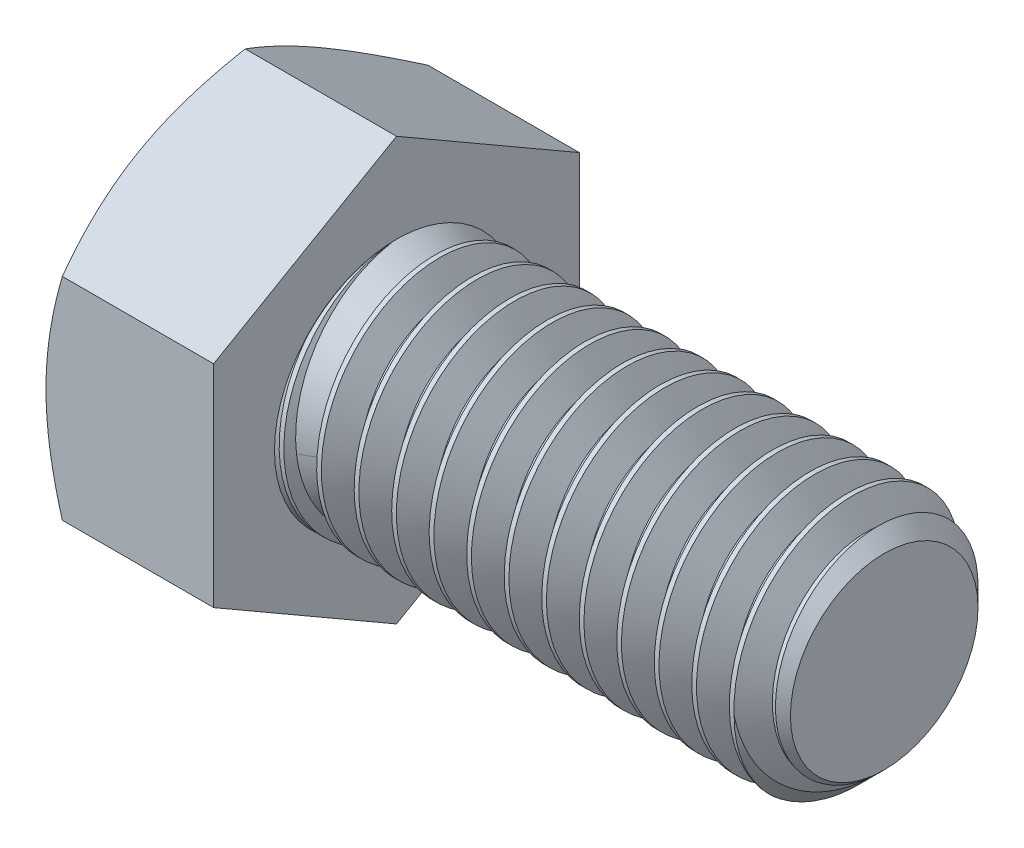
SolidWorks part; units mm, degrees
note: '?' marks a value the reader was unsure of.
ref_plane "Front Plane" through (0, 0, 0) normal (0, 0, 1) x (1, 0, 0)
ref_plane "Top Plane" through (0, 0, 0) normal (0, 1, 0) x (1, 0, 0)
ref_plane "Right Plane" through (0, 0, 0) normal (1, 0, 0) x (0, 0, -1)
sketch "Sketch1" plane through (0, 0, 0) normal (0, 0, 1) x (1, 0, 0)
  line L0 (-17.0656, 0) -> (17.0656, 0) construction
  line L1 (17.0656, 6.35) -> (17.0656, -6.35) construction
  line L2 (-8.3344, 9.525) -> (-8.3344, -9.525) construction
  line L3 (-17.0656, 9.525) -> (-17.0656, -9.525) construction
  line L4 (-8.5884, 6.3562) -> (-8.3344, 6.3562) construction
  line L5 (-8.3344, 6.3562) -> (2.6749, 0) construction
  line L6 (-8.5884, 6.3562) -> (-8.5884, 0) construction
  line L7 (-8.3344, 0) -> (-8.3344, 6.3562) construction
  point P9 (-8.3344, 0)
  point P10 (10.2272, -6.35)
  dimension "Screw Dia" = 12.7
  dimension "Hex" = 19.05
  dimension "Head Ht" = 8.7312
  dimension "Screw Length" = 25.4
  dimension "D1" = 6.8385
  dimension "D2" = 30
  dimension "D3" = 0.254
  dimension "MinThread" = 25.4
  dimension "D4" = 0.0124
ref_plane "Plane2" through (17.0656, 0, 0) normal (1, 0, 0) x (0, 0, -1)
sketch "Sketch5" plane through (17.0656, 0, 0) normal (1, 0, 0) x (0, 0, -1)
  circle A0 centre (0, 0) radius 6.35
extrude "Boss-Extrude3" add sketch "Sketch5" against normal up to vertex (25.4 mm away) up to point (-8.3344, 0, 0)
sketch "Sketch9" plane through (17.0656, 0, 0) normal (1, 0, 0) x (0, 0, -1)
  circle A1 centre (0, 0) radius 6.35
  circle A2 centre (0, 0) radius 6.35
  dimension "D1" = 0
chamfer "Chamfer1" distance 1.4654 angle 45 1 edges at (17.0656, 0, -6.35)
sketch "Sketch6" plane through (-8.3344, 0, 0) normal (-1, 0, 0) x (0, 0, 1)
  line L0 (0, 9.525) -> (0, -9.525) construction
  line L1 (9.525, 5.4993) -> (0, 10.9985)
  line L2 (0, 10.9985) -> (-9.525, 5.4993)
  line L3 (-9.525, 5.4993) -> (-9.525, -5.4993)
  line L4 (-9.525, -5.4993) -> (0, -10.9985)
  line L5 (0, -10.9985) -> (9.525, -5.4993)
  line L6 (9.525, -5.4993) -> (9.525, 5.4993)
  circle A0 centre (0, 0) radius 9.525 construction
extrude "Boss-Extrude4" add sketch "Sketch6" along normal up to vertex (8.7312 mm away) separate body up to point (-17.0656, -9.525, 0)
sketch "Sketch7" plane through (-17.0656, 0, 0) normal (-1, 0, 0) x (0, 0, 1)
  circle A0 centre (0, 0) radius 9.525 construction
  circle A1 centre (0, 0) radius 9.525
sketch "Sketch8" plane through (-17.0656, 0, 0) normal (-1, 0, 0) x (0, 0, 1)
  circle A0 centre (0, 0) radius 9.525 construction
  circle A1 centre (0, 0) radius 9.525
extrude "Cut-Extrude3" cut sketch "Sketch8" against normal through all draft 60 flip side to cut
sketch "Sketch12" plane through (-17.0656, 0, 0) normal (-1, 0, 0) x (0, 0, 1)
  line L0 (0, 7.3342) -> (0, 4.0958) construction
  line L1 (0.2857, 7.3342) -> (0.2858, 4.0958)
  line L2 (-0.2858, 7.3342) -> (-0.2857, 4.0958)
  line L3 (0, 6.35) -> (0, -6.35) construction
  arc A0 (0.2857, 7.3342) -> (-0.2858, 7.3342) centre (0, 7.3342) ccw
  arc A1 (-0.2857, 4.0958) -> (0.2858, 4.0958) centre (0, 4.0958) ccw
  circle A3 centre (0, 0) radius 3.81 construction
  circle A4 centre (0, 0) radius 7.62 construction
  point P2 (0, 5.715)
  dimension "D1" = 7.62
  dimension "D3" = 15.24
  dimension "D2" = 0.5715
extrude "Cut-Extrude4" cut sketch "Sketch12" against normal blind 0.254
pattern_circular "CirPattern1" count 6 over 360 about axis through (0, 0, 0) along (1, 0, 0) of "Cut-Extrude4"
curve "Helix/Spiral1" pitch 1.9538 height 27.3538 turns 14 parameters "Pitch"=1.9538
sketch "Sketch10" plane through (0, 0, 0) normal (0, 0, 1) x (1, 0, 0)
  line L0 (17.0656, 6.35) -> (17.7983, 5.0809)
  line L1 (17.7983, 5.0809) -> (18.0425, 5.0809)
  line L2 (18.0425, 5.0809) -> (18.7752, 6.35)
  line L3 (17.0656, 6.35) -> (18.7752, 6.35)
  line L4 (17.9204, 6.35) -> (17.9204, 5.0809) construction
  line L5 (17.432, 5.7155) -> (18.4089, 5.7155) construction
  dimension "D1" = 60
  dimension "D2" = 0.2442
  dimension "D3" = 0.9769
sweep "Cut-Sweep1" cut profiles "Sketch10" path "Helix/Spiral1" align with end faces yes
sketch "Sketch13" plane through (0, 0, 0) normal (0, 0, 1) x (1, 0, 0)
  line L0 (-17.0656, 0) -> (17.0656, 0) construction
  line L1 (-8.3344, 6.3562) -> (2.6749, 0) construction
  line L2 (-8.5884, 6.3562) -> (-8.3344, 6.3562) construction
  line L3 (-8.5884, 6.3562) -> (-8.5884, 0) construction
  line L4 (-8.5884, 0) -> (2.6749, 0)
  line L5 (-8.3344, 6.3562) -> (2.6749, 0)
  line L6 (-8.5884, 6.3562) -> (-8.3344, 6.3562)
  line L7 (-8.5884, 6.3562) -> (-8.5884, 0)
revolve "Revolve7" add sketch "Sketch13" angle 360 about L4
ref_axis "Center Axis 1" through (-8.3236, 0, 0) along (1, 0, 0)?
ref_plane "Contact Plane 1" through (-8.3344, 0, 0) normal (1, 0, 0) x (0, 0, -1)
equation "\"D2@Sketch10\" = \"Pitch@Helix/Spiral1\"*.125"
equation "\"D3@Sketch10\" = \"Pitch@Helix/Spiral1\"*.5"
equation "\"D3@Helix/Spiral1\" = \"Screw Length@Sketch1\" + \"Pitch@Helix/Spiral1\""
equation "\"D1@Chamfer1\" = \"Pitch@Helix/Spiral1\"*.75"
equation "\"D1@Sketch12\" = \"Hex@Sketch1\"*.4"
equation "\"D3@Sketch12\" = \"Hex@Sketch1\"*.8"
equation "\"D2@Sketch12\" = \"Hex@Sketch1\"*.03"
equation "\"D1@Sketch1\" = \"Pitch@Helix/Spiral1\"*3.5"
